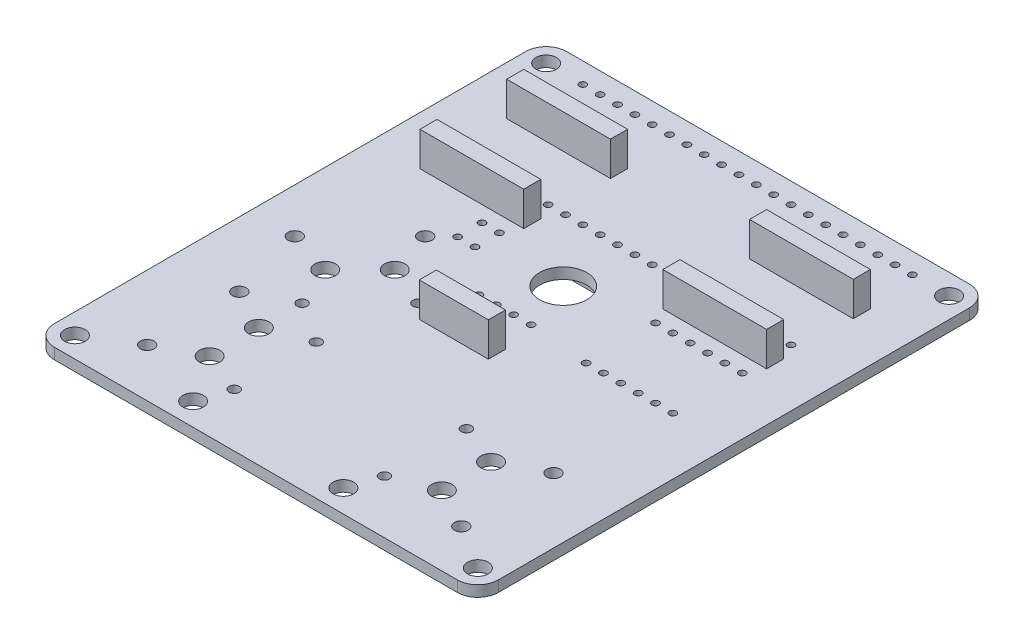
SolidWorks part; units mm, degrees
material "A-Glass Fiber"
ref_plane "Front Plane" through (0, 0, 0) normal (0, 0, 1) x (1, 0, 0)
ref_plane "Top Plane" through (0, 0, 0) normal (0, 1, 0) x (1, 0, 0)
ref_plane "Right Plane" through (0, 0, 0) normal (1, 0, 0) x (0, 0, -1)
sketch "main_body_sk" plane through (0, 0, 0) normal (0, 1, 0) x (1, 0, 0)
  line L0 (-32.5, 0) -> (32.5, 0) construction
  line L1 (-29.5, -57) -> (29.5, -57)
  line L2 (-32.5, -54) -> (-32.5, 15)
  line L3 (-29.5, 18) -> (29.5, 18)
  line L4 (32.5, -54) -> (32.5, 15)
  arc A0 (29.5, 18) -> (32.5, 15) centre (29.5, 15) cw
  arc A1 (32.5, -54) -> (29.5, -57) centre (29.5, -54) cw
  arc A2 (-29.5, -57) -> (-32.5, -54) centre (-29.5, -54) cw
  arc A3 (-32.5, 15) -> (-29.5, 18) centre (-29.5, 15) cw
  point P0 (0, 0)
  dimension "D1" = 3
  dimension "D2" = 65
  dimension "D3" = 57
  dimension "D4" = 59
  dimension "D5" = 69
  dimension "D6" = 18
  dimension "D7" = 15
  dimension "D8" = 29.5
  dimension "D9" = 57
  dimension "D10" = 54
  dimension "D11" = 69
  dimension "D12" = 75
extrude "main_body" add sketch "main_body_sk" along normal blind 1.6002 contours L3 A0 L4 A1 L1 A2 L2 A3
sketch "power_switch_sk" plane through (0, 1.6002, 0) normal (0, 1, 0) x (1, 0, 0)
  line L0 (0, -55) -> (0, 55) construction
  circle A0 centre (-29.5, 15) radius 1.5
  circle A1 centre (29.5, 15) radius 1.5
  circle A2 centre (29.5, -54) radius 1.5
  circle A3 centre (-29.5, -54) radius 1.5
  circle A4 centre (0, -12) radius 3.4544
  dimension "D1" = 3
  dimension "D3" = 6.9088
  dimension "D2" = 0
  dimension "D4" = 12
extrude "power_switch" cut sketch "power_switch_sk" against normal through all both and the other way through all
sketch "power_conn_sk" plane through (0, 1.6002, 0) normal (0, 1, 0) x (1, 0, 0)
  line L0 (-23, -36.425) -> (-23, -49.925) construction
  line L1 (-17, -39.575) -> (17, -39.575) construction
  line L2 (-17, -39.575) -> (-17, -46.775) construction
  line L3 (-17, -46.775) -> (17, -46.775) construction
  line L4 (17, -39.575) -> (17, -46.775) construction
  line L5 (-16.4241, -15.7888) -> (-25.97, -25.3347) construction
  line L6 (23, -36.425) -> (23, -49.925) construction
  line L7 (-23, -43.175) -> (-17, -43.175) construction
  line L8 (23, -43.175) -> (17, -43.175) construction
  line L9 (-16.9544, -24.8044) -> (-15.5402, -26.2186) construction
  line L10 (-11, -37.175) -> (-11, -49.175) construction
  line L11 (-17, -43.175) -> (-15, -43.175) construction
  line L12 (15, -35.35) -> (33.3, -35.35) construction
  line L13 (15, -35.35) -> (15, -51) construction
  line L18 (-14.4088, -22.2588) -> (-19.5, -27.35) construction
  line L19 (-16.9544, -24.8044) -> (-21.1971, -20.5618) construction
  line L20 (-22.9471, -7.7455) -> (-10.0071, -20.6855) construction
  line L21 (-22.9471, -7.7455) -> (-34.0134, -18.8117) construction
  line L22 (-34.0134, -18.8117) -> (-21.0733, -31.7517) construction
  line L23 (-10.0071, -20.6855) -> (-21.0733, -31.7517) construction
  line L24 (15, -51) -> (33.3, -51) construction
  line L25 (33.3, -35.35) -> (33.3, -51) construction
  line L26 (-33.3, -35.35) -> (-15, -35.35) construction
  line L27 (-33.3, -35.35) -> (-33.3, -51) construction
  line L28 (-33.3, -51) -> (-15, -51) construction
  line L29 (-15, -35.35) -> (-15, -51) construction
  line L30 (-29.5, -57) -> (29.5, -57) construction
  line L31 (17, -43.175) -> (15, -43.175) construction
  line L34 (11, -37.175) -> (11, -49.175) construction
  line L35 (-16.9544, -33.2897) -> (-8.4691, -24.8044) construction
  line L36 (-15.5402, -26.2186) -> (-12.7118, -29.0471) construction
  line L37 (-32.5, -54) -> (-32.5, 15) construction
  circle A0 centre (-17, -46.775) radius 1.5
  circle A1 centre (-17, -39.575) radius 1.5
  circle A2 centre (17, -39.575) radius 1.5
  circle A3 centre (17, -46.775) radius 1.5
  circle A4 centre (-23, -36.425) radius 1
  circle A5 centre (-23, -49.925) radius 1
  circle A6 centre (23, -36.425) radius 1
  circle A7 centre (23, -49.925) radius 1
  circle A17 centre (-25.97, -25.3347) radius 1
  circle A18 centre (-16.4241, -15.7888) radius 1
  circle A19 centre (-14.4088, -22.2588) radius 1.5
  circle A20 centre (-19.5, -27.35) radius 1.5
  circle A21 centre (-29.5, -54) radius 3 construction
  arc A22 (-32.5, -54) -> (-29.5, -57) centre (-29.5, -54) ccw construction
  circle A23 centre (-11, -37.175) radius 0.75
  circle A24 centre (-11, -49.175) radius 0.75
  circle A25 centre (11, -37.175) radius 0.75
  circle A26 centre (11, -49.175) radius 0.75
  circle A27 centre (-16.9544, -33.2897) radius 0.75
  circle A28 centre (-8.4691, -24.8044) radius 0.75
  point P8 (0, -39.575)
  point P14 (-23, -43.175)
  point P16 (-17, -43.175)
  point P42 (-12.7843, -27.35)
  point P44 (-10.1691, -27.35)
  point P55 (-28.4803, -13.2786)
  point P63 (-11, -43.175)
  point P64 (-8.3011, -27.35)
  point P69 (11, -43.175)
  point P74 (-12.7118, -29.0471)
  point P75 (-8.7281, -23.8098)
  dimension "D1" = 7.2
  dimension "D2" = 3
  dimension "D6" = 2
  dimension "D9" = 23
  dimension "D12" = 1.5
  dimension "D7" = 6
  dimension "D13" = 4
  dimension "D18" = 4
  dimension "D20" = 13
  dimension "D3" = 45
  dimension "D4" = 13.5
  dimension "D5" = 6
  dimension "D8" = 15.65
  dimension "D10" = 8
  dimension "D11" = 12
  dimension "D14" = 18.3
  dimension "D15" = 2
  dimension "D16" = 12
  dimension "D17" = 12
  dimension "D19" = 4
extrude "power_conn" cut sketch "power_conn_sk" against normal through all both and the other way through all
sketch "led_sk" plane through (0, 1.6002, 0) normal (0, 1, 0) x (1, 0, 0)
  line L0 (-5.08, -25.5) -> (-2.54, -25.5) construction
  line L1 (-2.54, -25.5) -> (0, -25.5) construction
  line L2 (0, -25.5) -> (2.54, -25.5) construction
  line L4 (-5.08, -19.25) -> (-2.54, -19.25) construction
  line L5 (-2.54, -19.25) -> (0, -19.25) construction
  line L6 (0, -19.25) -> (2.54, -19.25) construction
  circle A0 centre (-5.08, -25.5) radius 0.5
  circle A1 centre (-2.54, -25.5) radius 0.5
  circle A2 centre (0, -25.5) radius 0.5
  circle A3 centre (2.54, -25.5) radius 0.5
  circle A4 centre (-5.08, -19.25) radius 0.5
  circle A5 centre (-2.54, -19.25) radius 0.5
  circle A6 centre (0, -19.25) radius 0.5
  circle A7 centre (2.54, -19.25) radius 0.5
  dimension "D1" = 1
  dimension "D4" = 1
  dimension "D2" = 6.25
  dimension "D3" = 19.25
  dimension "D5" = 2.54
extrude "led" cut sketch "led_sk" against normal through all both and the other way through all
ref_axis "Axis1" through (0, 0, 12) along (0, 1, 0)
sketch "raspberrypi_sk" plane through (0, 1.6002, 0) normal (0, 1, 0) x (1, 0, 0)
  line L0 (-24.13, 15) -> (-25.527, 15) construction
  line L1 (-25.527, 16.651) -> (25.527, 16.651) construction
  line L2 (-25.527, 16.651) -> (-25.527, -4.431) construction
  line L3 (-25.527, -4.431) -> (25.527, -4.431) construction
  line L4 (25.527, 16.651) -> (25.527, -4.431) construction
  line L5 (-24.13, 15) -> (-24.13, -2.78) construction
  line L6 (-24.13, 15) -> (-24.13, 16.651) construction
  line L7 (-24.13, -2.78) -> (-24.13, -4.431) construction
  line L8 (-24.13, 15) -> (-21.59, 15) construction
  line L9 (-21.59, 15) -> (-19.05, 15) construction
  line L10 (-19.05, 15) -> (-16.51, 15) construction
  line L11 (-16.51, 15) -> (-13.97, 15) construction
  line L12 (-13.97, 15) -> (-11.43, 15) construction
  line L13 (-11.43, 15) -> (-8.89, 15) construction
  line L14 (-8.89, 15) -> (-6.35, 15) construction
  line L15 (-6.35, 15) -> (-3.81, 15) construction
  line L16 (-3.81, 15) -> (-1.27, 15) construction
  line L17 (-24.13, -2.78) -> (-21.59, -2.78) construction
  line L18 (-21.59, -2.78) -> (-19.05, -2.78) construction
  line L19 (-19.05, -2.78) -> (-16.51, -2.78) construction
  line L20 (-16.51, -2.78) -> (-13.97, -2.78) construction
  line L21 (-13.97, -2.78) -> (-11.43, -2.78) construction
  line L22 (-11.43, -2.78) -> (-8.89, -2.78) construction
  line L23 (-8.89, -2.78) -> (-6.35, -2.78) construction
  line L24 (-6.35, -2.78) -> (-3.81, -2.78) construction
  line L25 (-3.81, -2.78) -> (-1.27, -2.78) construction
  line L26 (-1.27, -2.78) -> (1.27, -2.78) construction
  line L27 (-1.27, 15) -> (1.27, 15) construction
  line L28 (1.27, 15) -> (3.81, 15) construction
  line L29 (3.81, 15) -> (6.35, 15) construction
  line L30 (6.35, 15) -> (8.89, 15) construction
  line L31 (8.89, 15) -> (11.43, 15) construction
  line L32 (11.43, 15) -> (13.97, 15) construction
  line L33 (13.97, 15) -> (16.51, 15) construction
  line L34 (16.51, 15) -> (19.05, 15) construction
  line L35 (19.05, 15) -> (21.59, 15) construction
  line L36 (21.59, 15) -> (24.13, 15) construction
  line L37 (1.27, -2.78) -> (3.81, -2.78) construction
  line L38 (3.81, -2.78) -> (6.35, -2.78) construction
  line L39 (6.35, -2.78) -> (8.89, -2.78) construction
  line L40 (8.89, -2.78) -> (11.43, -2.78) construction
  line L41 (11.43, -2.78) -> (13.97, -2.78) construction
  line L42 (13.97, -2.78) -> (16.51, -2.78) construction
  line L43 (16.51, -2.78) -> (19.05, -2.78) construction
  line L44 (19.05, -2.78) -> (21.59, -2.78) construction
  line L45 (21.59, -2.78) -> (24.13, -2.78) construction
  line L46 (0, 16.651) -> (0, 0) construction
  line L47 (-29.5, 18) -> (29.5, 18) construction
  line L48 (24.13, 15) -> (25.527, 15) construction
  line L49 (-0.9441, 0) -> (0.9441, 0) construction
  circle A0 centre (-24.13, 15) radius 0.508
  circle A1 centre (-24.13, -2.78) radius 0.508
  circle A2 centre (-21.59, 15) radius 0.508
  circle A3 centre (-19.05, 15) radius 0.508
  circle A4 centre (-16.51, 15) radius 0.508
  circle A5 centre (-13.97, 15) radius 0.508
  circle A6 centre (-11.43, 15) radius 0.508
  circle A7 centre (-8.89, 15) radius 0.508
  circle A8 centre (-6.35, 15) radius 0.508
  circle A9 centre (-3.81, 15) radius 0.508
  circle A10 centre (-1.27, 15) radius 0.508
  circle A11 centre (-21.59, -2.78) radius 0.508
  circle A12 centre (-19.05, -2.78) radius 0.508
  circle A13 centre (-16.51, -2.78) radius 0.508
  circle A14 centre (-13.97, -2.78) radius 0.508
  circle A15 centre (-11.43, -2.78) radius 0.508
  circle A16 centre (-8.89, -2.78) radius 0.508
  circle A17 centre (-6.35, -2.78) radius 0.508
  circle A18 centre (-3.81, -2.78) radius 0.508
  circle A19 centre (-1.27, -2.78) radius 0.508
  circle A20 centre (1.27, -2.78) radius 0.508
  circle A21 centre (1.27, 15) radius 0.508
  circle A22 centre (3.81, 15) radius 0.508
  circle A23 centre (6.35, 15) radius 0.508
  circle A24 centre (8.89, 15) radius 0.508
  circle A25 centre (11.43, 15) radius 0.508
  circle A26 centre (13.97, 15) radius 0.508
  circle A27 centre (16.51, 15) radius 0.508
  circle A28 centre (19.05, 15) radius 0.508
  circle A29 centre (21.59, 15) radius 0.508
  circle A30 centre (24.13, 15) radius 0.508
  circle A31 centre (3.81, -2.78) radius 0.508
  circle A32 centre (6.35, -2.78) radius 0.508
  circle A33 centre (8.89, -2.78) radius 0.508
  circle A34 centre (11.43, -2.78) radius 0.508
  circle A35 centre (13.97, -2.78) radius 0.508
  circle A36 centre (16.51, -2.78) radius 0.508
  circle A37 centre (19.05, -2.78) radius 0.508
  circle A38 centre (21.59, -2.78) radius 0.508
  circle A39 centre (24.13, -2.78) radius 0.508
  point P9 (0, 16.651)
  point P91 (-25.527, 6.11)
  dimension "D5" = 1.016
  dimension "D1" = 24.13
  dimension "D2" = 51.054
  dimension "D3" = 21.082
  dimension "D4" = 17.78
  dimension "D6" = 2.54
  dimension "D7" = 3
  dimension "D8" = 24.13
  dimension "D9" = 15
  dimension "D10" = 15
  dimension "D11" = 24.13
extrude "raspberrypi" cut sketch "raspberrypi_sk" against normal through all both and the other way through all
sketch "led_mount_sk" plane through (0, 1.6002, 0) normal (0, 1, 0) x (1, 0, 0)
  line L0 (-17, -39.575) -> (-17, -46.775) construction
  line L1 (-12.5, -53.693) -> (9.5, -53.693) construction
  circle A0 centre (-12.5, -53.693) radius 1.5
  circle A1 centre (-29.5, -54) radius 1.5 construction
  circle A2 centre (9.5, -53.693) radius 1.5
  circle A3 centre (29.5, -54) radius 1.5 construction
  point P5 (0, 0)
  point P10 (0, -53.693)
  point P14 (0, 0)
  point P16 (11.5693, -53.693)
  point P17 (0, 0)
  dimension "D1" = 12.5
  dimension "D2" = 9.5
extrude "led_mount" cut sketch "led_mount_sk" against normal through all both and the other way through all
sketch "accel_sk" plane through (0, 1.6002, 0) normal (0, 1, 0) x (1, 0, 0)
  line L0 (-24.13, 6.35) -> (-21.59, 6.35) construction
  line L1 (-27.53, 8.875) -> (-8.03, 8.875) construction
  line L2 (-30.53, 5.875) -> (-30.53, -5.875) construction
  line L3 (-27.53, -8.875) -> (-8.03, -8.875) construction
  line L4 (-5.03, 5.875) -> (-5.03, -5.875) construction
  line L5 (-21.59, 6.35) -> (-19.05, 6.35) construction
  line L6 (-19.05, 6.35) -> (-16.51, 6.35) construction
  line L7 (-16.51, 6.35) -> (-13.97, 6.35) construction
  line L8 (-13.97, 6.35) -> (-11.43, 6.35) construction
  line L9 (-24.13, -6.35) -> (-21.59, -6.35) construction
  line L10 (-21.59, -6.35) -> (-19.05, -6.35) construction
  line L11 (-19.05, -6.35) -> (-16.51, -6.35) construction
  line L12 (-16.51, -6.35) -> (-13.97, -6.35) construction
  line L13 (-13.97, -6.35) -> (-11.43, -6.35) construction
  line L14 (-24.13, 6.35) -> (-24.13, -6.35) construction
  line L15 (-30.53, 0) -> (-24.13, 0) construction
  line L16 (-11.43, 6.35) -> (-5.03, 6.35) construction
  line L17 (11.43, 6.35) -> (13.97, 6.35) construction
  line L18 (8.03, 8.875) -> (27.53, 8.875) construction
  line L19 (5.03, 5.875) -> (5.03, -5.875) construction
  line L20 (8.03, -8.875) -> (27.53, -8.875) construction
  line L21 (30.53, 5.875) -> (30.53, -5.875) construction
  line L22 (13.97, 6.35) -> (16.51, 6.35) construction
  line L23 (16.51, 6.35) -> (19.05, 6.35) construction
  line L24 (19.05, 6.35) -> (21.59, 6.35) construction
  line L25 (21.59, 6.35) -> (24.13, 6.35) construction
  line L26 (11.43, -6.35) -> (13.97, -6.35) construction
  line L27 (13.97, -6.35) -> (16.51, -6.35) construction
  line L28 (16.51, -6.35) -> (19.05, -6.35) construction
  line L29 (19.05, -6.35) -> (21.59, -6.35) construction
  line L30 (21.59, -6.35) -> (24.13, -6.35) construction
  line L31 (11.43, 6.35) -> (11.43, -6.35) construction
  line L32 (5.03, 0) -> (11.43, 0) construction
  line L33 (24.13, 6.35) -> (30.53, 6.35) construction
  line L34 (24.13, 6.35) -> (24.13, -6.35) construction
  line L35 (-11.43, 6.35) -> (-11.43, 0) construction
  line L36 (-5.03, 0) -> (0, 0) construction
  line L37 (0, 0) -> (5.03, 0) construction
  line L38 (-11.43, 0) -> (-5.03, 0) construction
  circle A0 centre (-24.13, 6.35) radius 0.508
  circle A1 centre (-21.59, 6.35) radius 0.508
  circle A2 centre (-19.05, 6.35) radius 0.508
  circle A3 centre (-16.51, 6.35) radius 0.508
  circle A4 centre (-13.97, 6.35) radius 0.508
  circle A5 centre (-11.43, 6.35) radius 0.508
  circle A6 centre (-24.13, -6.35) radius 0.508
  circle A7 centre (-21.59, -6.35) radius 0.508
  circle A8 centre (-19.05, -6.35) radius 0.508
  circle A9 centre (-16.51, -6.35) radius 0.508
  circle A10 centre (-13.97, -6.35) radius 0.508
  circle A11 centre (-11.43, -6.35) radius 0.508
  arc A12 (-8.03, 8.875) -> (-5.03, 5.875) centre (-8.03, 5.875) cw construction
  arc A13 (-5.03, -5.875) -> (-8.03, -8.875) centre (-8.03, -5.875) cw construction
  arc A14 (-27.53, -8.875) -> (-30.53, -5.875) centre (-27.53, -5.875) cw construction
  arc A15 (-30.53, 5.875) -> (-27.53, 8.875) centre (-27.53, 5.875) cw construction
  circle A16 centre (0, 0) radius 5.5 construction
  circle A17 centre (11.43, 6.35) radius 0.508
  circle A18 centre (13.97, 6.35) radius 0.508
  circle A19 centre (16.51, 6.35) radius 0.508
  circle A20 centre (19.05, 6.35) radius 0.508
  circle A21 centre (21.59, 6.35) radius 0.508
  circle A22 centre (24.13, 6.35) radius 0.508
  circle A23 centre (11.43, -6.35) radius 0.508
  circle A24 centre (13.97, -6.35) radius 0.508
  circle A25 centre (16.51, -6.35) radius 0.508
  circle A26 centre (19.05, -6.35) radius 0.508
  circle A27 centre (21.59, -6.35) radius 0.508
  circle A28 centre (24.13, -6.35) radius 0.508
  arc A29 (27.53, 8.875) -> (30.53, 5.875) centre (27.53, 5.875) cw construction
  arc A30 (30.53, -5.875) -> (27.53, -8.875) centre (27.53, -5.875) cw construction
  arc A31 (8.03, -8.875) -> (5.03, -5.875) centre (8.03, -5.875) cw construction
  arc A32 (5.03, 5.875) -> (8.03, 8.875) centre (8.03, 5.875) cw construction
  point P28 (-17.78, 6.35)
  point P32 (-5.03, 8.875)
  point P40 (-17.78, 8.875)
  point P91 (-24.13, -2.78)
  dimension "D2" = 1.016
  dimension "D6" = 3
  dimension "D8" = 11
  dimension "D10" = 1.016
  dimension "D1" = 2.54
  dimension "D3" = 12.7
  dimension "D4" = 25.5
  dimension "D5" = 17.75
  dimension "D9" = 2.54
  dimension "D11" = 12.7
extrude "accel" cut sketch "accel_sk" against normal through all both and the other way through all
sketch "logicshift_sk" plane through (0, 1.6002, 0) normal (0, 1, 0) x (1, 0, 0)
  line L0 (11.43, -9.92) -> (11.43, -20.08) construction
  line L1 (11.43, -9.92) -> (13.97, -9.92) construction
  line L2 (13.97, -9.92) -> (16.51, -9.92) construction
  line L3 (16.51, -9.92) -> (19.05, -9.92) construction
  line L4 (19.05, -9.92) -> (21.59, -9.92) construction
  line L5 (21.59, -9.92) -> (24.13, -9.92) construction
  line L6 (24.13, -6.35) -> (24.13, -9.92) construction
  line L7 (11.43, -20.08) -> (13.97, -20.08) construction
  line L8 (13.97, -20.08) -> (16.51, -20.08) construction
  line L9 (16.51, -20.08) -> (19.05, -20.08) construction
  line L10 (19.05, -20.08) -> (21.59, -20.08) construction
  line L11 (21.59, -20.08) -> (24.13, -20.08) construction
  circle A1 centre (11.43, -9.92) radius 0.508
  circle A2 centre (13.97, -9.92) radius 0.508
  circle A3 centre (16.51, -9.92) radius 0.508
  circle A4 centre (19.05, -9.92) radius 0.508
  circle A5 centre (21.59, -9.92) radius 0.508
  circle A6 centre (24.13, -9.92) radius 0.508
  circle A7 centre (11.43, -20.08) radius 0.508
  circle A8 centre (13.97, -20.08) radius 0.508
  circle A9 centre (16.51, -20.08) radius 0.508
  circle A10 centre (19.05, -20.08) radius 0.508
  circle A11 centre (21.59, -20.08) radius 0.508
  circle A12 centre (24.13, -20.08) radius 0.508
  point P24 (11.43, -15)
  point P25 (17.78, -9.92)
  dimension "D1" = 1.016
  dimension "D2" = 10.16
  dimension "D3" = 15
  dimension "D5" = 2.54
extrude "logicshift" cut sketch "logicshift_sk" against normal through all both and the other way through all
sketch "esc_sk" plane through (0, 0, 0) normal (0, -1, 0) x (1, 0, 0)
  line L0 (-11.43, 6.35) -> (-11.43, 2.78) construction
  line L1 (-13.97, 9.92) -> (-13.97, 6.35) construction
  line L2 (-11.43, 6.35) -> (-13.97, 6.35) construction
  line L3 (-13.97, 9.92) -> (-11.43, 9.92) construction
  line L4 (-13.97, 13.49) -> (-11.43, 13.49) construction
  line L5 (-13.97, 13.49) -> (-13.97, 9.92) construction
  line L6 (-13.97, 13.49) -> (-15.22, 13.49) construction
  line L7 (-15.22, 14.74) -> (-10.18, 14.74) construction
  line L8 (-15.22, 14.74) -> (-15.22, 12.24) construction
  line L9 (-15.22, 12.24) -> (-10.18, 12.24) construction
  line L10 (-10.18, 14.74) -> (-10.18, 12.24) construction
  line L11 (-10.18, 13.49) -> (-11.43, 13.49) construction
  circle A0 centre (-13.97, 9.92) radius 0.508
  circle A1 centre (-11.43, 13.49) radius 0.508
  circle A2 centre (-13.97, 13.49) radius 0.508
  circle A3 centre (-11.43, 9.92) radius 0.508
  circle A4 centre (-11.43, 6.35) radius 0.508 construction
  dimension "D1" = 2.5
  dimension "D2" = 1.25
extrude "esc" cut sketch "esc_sk" against normal through all both and the other way through all
sketch "top_female_headers_sk" plane through (0, 0, 0) normal (0, -1, 0) x (1, 0, 0)
  line L0 (24.13, 9.92) -> (25.38, 9.92) construction
  line L9 (-25.38, 4.03) -> (25.38, 4.03)
  line L10 (-25.38, 4.03) -> (-25.38, 1.53)
  line L11 (-25.38, 1.53) -> (25.38, 1.53)
  line L12 (25.38, 4.03) -> (25.38, 1.53)
  line L17 (-24.13, 2.78) -> (-25.38, 2.78) construction
  line L18 (24.13, 2.78) -> (25.38, 2.78) construction
  line L19 (-24.13, -15) -> (-25.38, -15) construction
  line L20 (-25.38, -13.75) -> (25.38, -13.75)
  line L21 (-25.38, -13.75) -> (-25.38, -16.25)
  line L22 (-25.38, -16.25) -> (25.38, -16.25)
  line L23 (25.38, -13.75) -> (25.38, -16.25)
  line L24 (-24.13, -15) -> (-24.13, -13.75) construction
  line L25 (-24.13, -15) -> (-24.13, -16.25) construction
  line L26 (24.13, -15) -> (25.38, -15) construction
  line L27 (-6.33, 20.5) -> (3.79, 20.5)
  line L28 (-6.33, 20.5) -> (-6.33, 18)
  line L29 (-6.33, 18) -> (3.79, 18)
  line L30 (3.79, 20.5) -> (3.79, 18)
  line L31 (10.18, 11.17) -> (25.38, 11.17)
  line L32 (10.18, 11.17) -> (10.18, 8.67)
  line L33 (10.18, 8.67) -> (25.38, 8.67)
  line L34 (25.38, 11.17) -> (25.38, 8.67)
  line L35 (10.18, 21.33) -> (25.38, 21.33)
  line L36 (10.18, 21.33) -> (10.18, 18.83)
  line L37 (10.18, 18.83) -> (25.38, 18.83)
  line L38 (25.38, 21.33) -> (25.38, 18.83)
  line L39 (24.13, 20.08) -> (25.38, 20.08) construction
  line L40 (11.43, 9.92) -> (10.18, 9.92) construction
  line L41 (-5.08, 19.25) -> (-6.33, 19.25) construction
  line L42 (3.79, 19.25) -> (2.54, 19.25) construction
  point P14 (0, 0)
  dimension "D1" = 2.5
  dimension "D2" = 1.25
extrude "top_female_headers" add sketch "top_female_headers_sk" along normal blind 5
sketch "bot_female_headers_sk" plane through (0, 1.6002, 0) normal (0, 1, 0) x (1, 0, 0)
  line L0 (-24.13, 6.35) -> (-25.38, 6.35) construction
  line L1 (-25.38, 7.6) -> (-10.18, 7.6)
  line L2 (-25.38, 7.6) -> (-25.38, 5.1)
  line L3 (-25.38, 5.1) -> (-10.18, 5.1)
  line L4 (-10.18, 7.6) -> (-10.18, 5.1)
  line L5 (10.18, 7.6) -> (25.38, 7.6)
  line L6 (10.18, 7.6) -> (10.18, 5.1)
  line L7 (10.18, 5.1) -> (25.38, 5.1)
  line L8 (25.38, 7.6) -> (25.38, 5.1)
  line L9 (-25.38, -5.1) -> (-10.18, -5.1)
  line L10 (-25.38, -5.1) -> (-25.38, -7.6)
  line L11 (-25.38, -7.6) -> (-10.18, -7.6)
  line L12 (-10.18, -5.1) -> (-10.18, -7.6)
  line L13 (10.18, -5.1) -> (25.38, -5.1)
  line L14 (10.18, -5.1) -> (10.18, -7.6)
  line L15 (10.18, -7.6) -> (25.38, -7.6)
  line L16 (25.38, -5.1) -> (25.38, -7.6)
  line L17 (-24.13, -6.35) -> (-25.38, -6.35) construction
  line L18 (-10.18, 6.35) -> (-11.43, 6.35) construction
  line L19 (24.13, 6.35) -> (25.38, 6.35) construction
  line L20 (25.38, -6.35) -> (24.13, -6.35) construction
  line L21 (-5.08, -25.5) -> (-6.33, -25.5) construction
  line L22 (-6.33, -24.25) -> (3.79, -24.25)
  line L23 (-6.33, -24.25) -> (-6.33, -26.75)
  line L24 (-6.33, -26.75) -> (3.79, -26.75)
  line L25 (3.79, -24.25) -> (3.79, -26.75)
  line L26 (2.54, -25.5) -> (3.79, -25.5) construction
  dimension "D1" = 2.5
  dimension "D2" = 1.25
extrude "bot_female_headers" add sketch "bot_female_headers_sk" along normal blind 5
sketch "top_male_headers_sk" plane through (0, 0, 0) normal (0, -1, 0) x (1, 0, 0)
  line L0 (-13.97, 9.92) -> (-15.22, 9.92) construction
  line L1 (-15.22, 14.74) -> (-10.18, 14.74)
  line L2 (-15.22, 14.74) -> (-15.22, 12.24)
  line L3 (-15.22, 12.24) -> (-10.18, 12.24)
  line L4 (-10.18, 14.74) -> (-10.18, 12.24)
  line L5 (-15.22, 11.17) -> (-10.18, 11.17)
  line L6 (-15.22, 11.17) -> (-15.22, 8.67)
  line L7 (-15.22, 8.67) -> (-10.18, 8.67)
  line L8 (-10.18, 11.17) -> (-10.18, 8.67)
  line L9 (-13.97, 13.49) -> (-15.22, 13.49) construction
  line L10 (-11.43, 9.92) -> (-10.18, 9.92) construction
  point P17 (-9.1301, 9.92)
  dimension "D1" = 2.5
  dimension "D2" = 1.25
extrude "top_male_headers" add sketch "top_male_headers_sk" along normal blind 2.5
sketch "top_male_header_pins_sk" plane through (0, -2.5, 0) normal (0, -1, 0) x (1, 0, 0)
  circle A0 centre (-13.97, 13.49) radius 0.5
  circle A1 centre (-11.43, 13.49) radius 0.5
  circle A2 centre (-11.43, 9.92) radius 0.5
  circle A3 centre (-13.97, 9.92) radius 0.5
  dimension "D1" = 1
extrude "top_male_header_pins" add sketch "top_male_header_pins_sk" along normal blind 5
